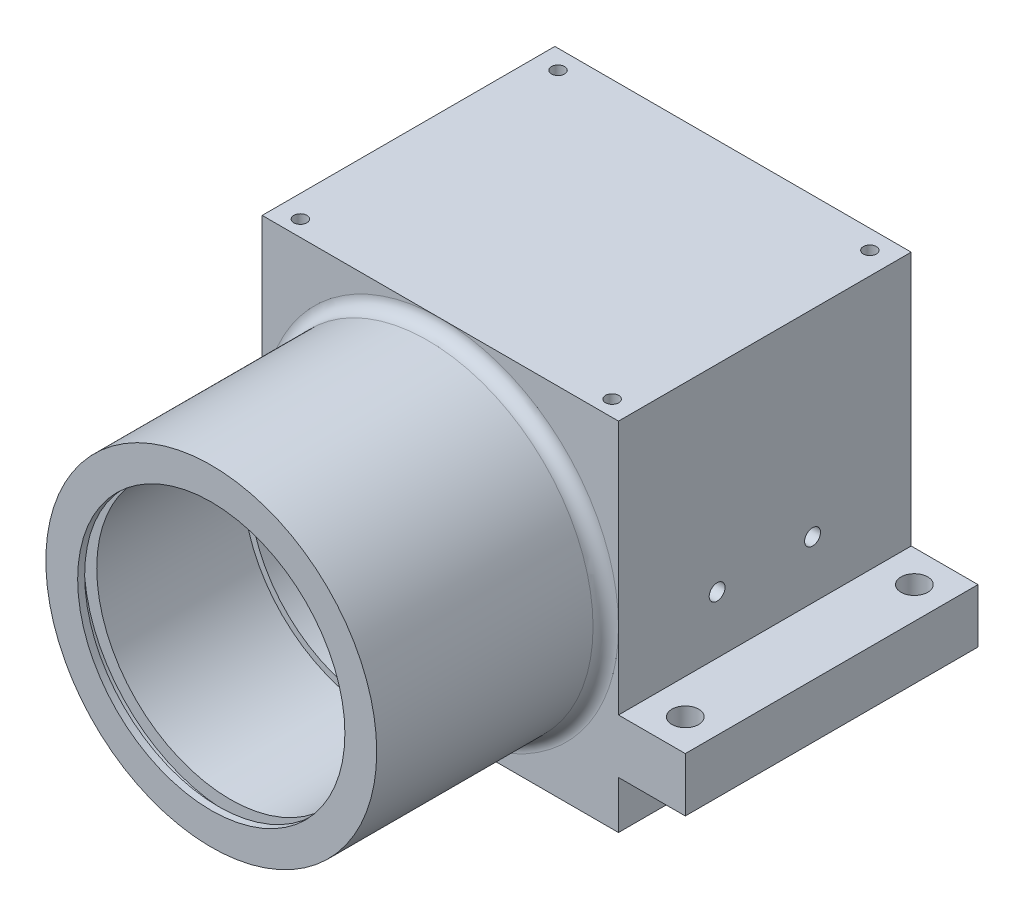
SolidWorks part; units mm, degrees
material "1060 合金"
ref_plane "前视基准面" through (0, 0, 0) normal (0, 0, 1) x (1, 0, 0)
ref_plane "上视基准面" through (0, 0, 0) normal (0, 1, 0) x (1, 0, 0)
ref_plane "右视基准面" through (0, 0, 0) normal (1, 0, 0) x (0, 0, -1)
sketch "草图1" plane through (0, 0, 0) normal (0, 0, 1) x (1, 0, 0)
  line L0 (0, -28) -> (0, 33.0223) construction
  line L1 (-28, -28) -> (28, -28)
  line L2 (-28, -28) -> (-28, 28)
  line L3 (-28, 28) -> (28, 28)
  line L4 (28, -28) -> (28, 28)
  line L5 (0, 0) -> (56.6994, 0) construction
  circle A0 centre (0, 0) radius 24 construction
  point P9 (0, 24)
  point P10 (0, -24)
  point P12 (24, 0)
  dimension "D1" = 4
  dimension "D2" = 48
  dimension "D3" = 4
  dimension "D4" = 4
extrude "凸台-拉伸1" add sketch "草图1" along normal blind 82
sketch "草图3" plane through (0, 0, 0) normal (1, 0, 0) x (0, 0, -1)
  line L0 (5.7193, 0) -> (-112.2198, 0) construction
  line L1 (0, -28) -> (0, 28) construction
  line L2 (-82, 0) -> (0, 0)
  line L3 (-82, 28) -> (-82, -28) construction
  line L4 (-82, 21) -> (-56, 21)
  line L5 (0, 0) -> (0, 23)
  line L7 (-52, 23) -> (0, 23)
  line L9 (-56, 21) -> (-56, 20)
  line L10 (-56, 20) -> (-52, 20)
  line L11 (-52, 23) -> (-52, 20)
  line L12 (-82, 0) -> (-82, 21)
  dimension "D1" = 20
  dimension "D2" = 21
  dimension "D3" = 4
  dimension "D4" = 23
  dimension "D5" = 26
revolve "切除-旋转2" cut sketch "草图3" angle 360 about L0
sketch "草图4" plane through (0, 0, 82) normal (0, 0, 1) x (1, 0, 0)
  line L0 (28, 28) -> (-28, 28) construction
  line L1 (-28, 28) -> (-28, -28) construction
  line L2 (-28, -28) -> (28, -28) construction
  line L3 (28, -28) -> (28, 28) construction
  line L4 (28, 28) -> (-28, 28)
  line L5 (-28, 28) -> (-28, -28)
  line L6 (-28, -28) -> (28, -28)
  line L7 (28, -28) -> (28, 28)
  circle A2 centre (0, 0) radius 26
  dimension "D1" = 52
chamfer "倒角1" [suppressed] distance 15 angle 45
extrude "切除-拉伸1" cut sketch "草图4" against normal blind 36
hole_wizard "M4 螺纹孔1" positions "草图12" profile "草图11" tap size "M4" standard "GB"
sketch "草图12" plane through (0, 0, 0) normal (0, 0, -1) x (-1, 0, 0)
  line L0 (0, 0) -> (0, 40.8365) construction
  line L11 (0, 0) -> (18.3848, 18.3848) construction
  circle A3 centre (0, 0) radius 26
  circle A4 centre (0, 0) radius 26 construction
  point P0 (18.3848, 18.3848)
  point P116 (18.3848, -18.3848)
  point P117 (-18.3848, -18.3848)
  point P118 (-18.3848, 18.3848)
  dimension "D1" = 45
  dimension "D2" = 4
  dimension "D3" = 3
sketch "草图11" plane through (-18.3848, 18.3848, 0) normal (1, 0, 0) x (0, 1, 0)
  line L0 (0, 0) -> (0, 11.0914)
  line L1 (0, 11.0914) -> (1.65, 10.1)
  line L2 (1.65, 10.1) -> (1.65, 0)
  line L5 (1.65, 0) -> (0, 0)
  line L10 (0, 11.0914) -> (-1.65, 10.1) construction
  line L11 (0, -6.35) -> (0, 107.95) construction
  dimension "螺纹孔钻头直径" = 3.3
  dimension "螺纹孔钻头深度" = 10.1
  dimension "导头角度" = 118
cosmetic thread "孔螺蚊线5" parameters "D1"=8, "D2"=4
cosmetic thread "孔螺蚊线6" parameters "D1"=8, "D2"=4
cosmetic thread "孔螺蚊线7" parameters "D1"=8, "D2"=4
cosmetic thread "孔螺蚊线8" parameters "D1"=8, "D2"=4
sketch "草图15" plane through (0, 0, 0) normal (0, 1, 0) x (1, 0, 0)
  line L0 (0, 0) -> (0, -98.0138) construction
  line L1 (-26, -82) -> (26, -82) construction
  line L2 (0, -80.9) -> (-23, -80.9)
  line L3 (0, -80.9) -> (0, -79)
  line L4 (0, -79) -> (-23, -79)
  line L5 (-23, -80.9) -> (-23, -79)
  dimension "D1" = 23
  dimension "D2" = 3
  dimension "D3" = 1.9
revolve "切除-旋转3" cut sketch "草图15" angle 360 about L0
fillet "圆角1" radius 2 1 edges at (26, 0, 46)
chamfer "倒角2" distance 1 angle 45 1 edges at (-23, 0, 0)
hole_wizard "M2.5 螺纹孔1" positions "草图18" profile "草图17" tap size "M2.5" standard "GB"
sketch "草图18" plane through (0, 28, 0) normal (0, 1, 0) x (1, 0, 0)
  line L0 (0, 0) -> (0, -42.6299) construction
  line L3 (-24.5, -43.5) -> (24.5, -43.5) construction
  line L4 (-24.5, -43.5) -> (-24.5, -3) construction
  line L5 (-24.5, -3) -> (24.5, -3) construction
  line L6 (24.5, -43.5) -> (24.5, -3) construction
  line L7 (-24.5, -43.5) -> (24.5, -3) construction
  line L8 (-24.5, -3) -> (24.5, -43.5) construction
  line L9 (28, 0) -> (-28, 0) construction
  point P7 (24.5, -3)
  point P92 (-24.5, -43.5)
  point P93 (-24.5, -3)
  point P94 (24.5, -43.5)
  dimension "D1" = 49
  dimension "D2" = 40.5
  dimension "D3" = 3
sketch "草图17" plane through (24.5, 28, 3) normal (1, 0, 0) x (0, 0, 1)
  line L0 (0, 0) -> (0, 7.8659)
  line L1 (0, 7.8659) -> (1.025, 7.25)
  line L2 (1.025, 7.25) -> (1.025, 0)
  line L5 (1.025, 0) -> (0, 0)
  line L10 (0, 7.8659) -> (-1.025, 7.25) construction
  line L11 (0, -6.35) -> (0, 107.95) construction
  dimension "螺纹孔钻头直径" = 2.05
  dimension "螺纹孔钻头深度" = 7.25
  dimension "导头角度" = 118
cosmetic thread "孔螺蚊线9" parameters "D1"=5, "D2"=2.5
cosmetic thread "孔螺蚊线10" parameters "D1"=5, "D2"=2.5
cosmetic thread "孔螺蚊线11" parameters "D1"=5, "D2"=2.5
cosmetic thread "孔螺蚊线12" parameters "D1"=5, "D2"=2.5
sketch "草图19" plane through (0, -28, 0) normal (0, -1, 0) x (1, 0, 0)
  line L0 (-28, 0) -> (28, 0) construction
  line L1 (-38.5, 0) -> (38.5, 0)
  line L2 (-38.5, 0) -> (-38.5, 46)
  line L3 (-38.5, 46) -> (38.5, 46)
  line L4 (38.5, 0) -> (38.5, 46)
  line L5 (-38.5, 0) -> (38.5, 46) construction
  line L6 (-38.5, 46) -> (38.5, 0) construction
  line L7 (28, 46) -> (28, 0) construction
  line L8 (28, 46) -> (0, 46) construction
  point P0 (0, 23)
  line M2 (-28, 46) -> (-28, 0)
  line M4 (28, 0) -> (28, 46)
  dimension "D1" = 10.5
extrude "凸台-拉伸2" add sketch "草图19" against normal blind 16 contours L1 L4 L3 M4 | L3 L2 L1 M2 region at (-33.25, -28, 23) region at (33.25, -28, 23)
hole_wizard "M5 螺纹孔1" positions "草图21" profile "草图20" tap size "M5" standard "GB" end condition up to next
sketch "草图21" plane through (0, -28, 0) normal (0, -1, 0) x (-1, 0, 0)
  line L1 (-33.5, -41) -> (33.5, -41) construction
  line L2 (-33.5, -41) -> (-33.5, -5) construction
  line L3 (-33.5, -5) -> (33.5, -5) construction
  line L4 (33.5, -41) -> (33.5, -5) construction
  line L5 (-33.5, -41) -> (33.5, -5) construction
  line L6 (-33.5, -5) -> (33.5, -41) construction
  line L7 (0, 0) -> (0, -56.3467) construction
  line L9 (38.5, -46) -> (0, -46) construction
  line L10 (38.5, 0) -> (-38.5, 0) construction
  point P3 (33.5, -5)
  point P78 (-33.5, -41)
  point P79 (-33.5, -5)
  point P80 (33.5, -41)
  dimension "D1" = 67
  dimension "D2" = 5
  dimension "D3" = 5
sketch "草图20" plane through (-33.5, -28, 5) normal (1, 0, 0) x (0, 0, -1)
  line L0 (0, 0) -> (0, 16)
  line L1 (0, 16) -> (2.1, 16)
  line L2 (2.1, 16) -> (2.1, 0)
  line L5 (2.1, 0) -> (0, 0)
  line L11 (0, -6.35) -> (0, 107.95) construction
  dimension "通孔螺纹孔钻头直径" = 4.2
  dimension "通孔螺纹孔钻头深度" = 16
cosmetic thread "孔螺蚊线13" parameters "D2"=5
cosmetic thread "孔螺蚊线14" parameters "D2"=5
cosmetic thread "孔螺蚊线15" parameters "D2"=5
cosmetic thread "孔螺蚊线16" parameters "D2"=5
hole_wizard "M3 螺纹孔1" positions "草图23" profile "草图24" tap size "M3" standard "GB"
sketch "草图23" plane through (28, 0, 0) normal (1, 0, 0) x (0, 0, -1)
  line L0 (-23, 28) -> (-23, -39.4535) construction
  line L1 (-46, 28) -> (0, 28) construction
  line L3 (0, -28) -> (-46, -28) construction
  point P0 (-30.5, -3)
  point P2 (-15.5, -3)
  dimension "D1" = 15
  dimension "D2" = 25
sketch "草图24" plane through (28, -3, 30.5) normal (0, 1, 0) x (0, 0, -1)
  line L0 (0, 0) -> (0, 6.2511)
  line L1 (0, 6.2511) -> (1.25, 5.5)
  line L2 (1.25, 5.5) -> (1.25, 0)
  line L5 (1.25, 0) -> (0, 0)
  line L10 (0, 6.2511) -> (-1.25, 5.5) construction
  line L11 (0, -6.35) -> (0, 107.95) construction
  dimension "螺纹孔钻头直径" = 2.5
  dimension "螺纹孔钻头深度" = 5.5
  dimension "导头角度" = 118
cosmetic thread "孔螺蚊线17" parameters "D1"=5.5, "D2"=3
cosmetic thread "孔螺蚊线18" parameters "D1"=5.5, "D2"=3
sketch "草图25" plane through (0, 0, 0) normal (0, 0, -1) x (-1, 0, 0)
  line L0 (-28, -12) -> (-38.5, -12) construction
  line L1 (-38.5, -28) -> (-28, -28)
  line L2 (-38.5, -28) -> (-38.5, -20.5)
  line L3 (-38.5, -20.5) -> (-28, -20.5)
  line L4 (-28, -28) -> (-28, -20.5)
  dimension "D1" = 8.5
extrude "切除-拉伸2" cut sketch "草图25" against normal up to next
mirror "镜向1" about plane through (0, 0, 0) normal (1, 0, 0) of "切除-拉伸2", "M3 螺纹孔1"
